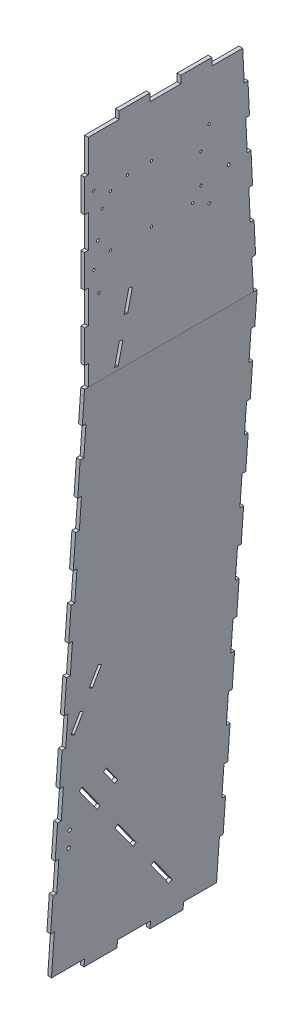
SolidWorks part; units mm, degrees
ref_plane "Front Plane" through (0, 0, 0) normal (0, 0, 1) x (1, 0, 0)
ref_plane "Top Plane" through (0, 0, 0) normal (0, 1, 0) x (1, 0, 0)
ref_plane "Right Plane" through (0, 0, 0) normal (1, 0, 0) x (0, 0, -1)
sketch "Sketch1" plane through (0, 0, 0) normal (0, 0, 1) x (1, 0, 0)
  line L0 (-215.8818, 2052.32) -> (-215.8818, 1463.04)
  line L1 (-215.8818, 1463.04) -> (-316.0886, 20.32)
  line L2 (-316.0886, 20.32) -> (-317.5, 0)
  line L4 (-215.8818, 2052.32) -> (-215.8818, 2072.64)
  line L6 (-215.8818, 2072.64) -> (-205.7153, 2072.64)
  line L7 (-205.7153, 2072.64) -> (-205.7153, 1463.04)
  line L8 (-205.7153, 1463.04) -> (-307.3335, 0)
  line L9 (-317.5, 0) -> (-307.3335, 0)
  line L10 (-371.5407, 0) -> (-280.9748, 0) construction
  line L13 (-371.5407, 20.32) -> (-280.9748, 20.32) construction
  line L15 (-205.7153, 1463.04) -> (205.7153, 1463.04) construction
  point P23 (-305.9221, 20.32)
  dimension "D1" = 307.3335
extrude "Boss-Extrude1" add sketch "Sketch1" against normal blind 469.9
sketch "Sketch2" plane through (-315.9757, 21.9467, 0) normal (-0.9976, 0.0693, 0) x (0, 0, 1)
  line L35 (0, 1355.6785) -> (0, 0.1049)
  line L37 (-234.95, 1444.5652) -> (-234.95, -21.9996) construction
  line L40 (-10.16, 0.1049) -> (0, 0.1049)
  line L43 (-10.16, 0.1049) -> (-10.16, -21.9996)
  line L46 (0, 1272.0274) -> (-10.16, 1272.0274)
  line L47 (-10.16, 1355.6785) -> (-10.16, 1272.0274)
  line L48 (0, 1355.6785) -> (-10.16, 1355.6785)
  line L49 (0, 1177.9051) -> (-10.16, 1177.9051)
  line L50 (-10.16, 1177.9051) -> (-10.16, 1094.2274)
  line L51 (0, 1094.2274) -> (-10.16, 1094.2274)
  line L52 (0, 916.4274) -> (-10.16, 916.4274)
  line L53 (-10.16, 1000.1317) -> (-10.16, 916.4274)
  line L54 (0, 1000.1317) -> (-10.16, 1000.1317)
  line L55 (0, 822.3583) -> (-10.16, 822.3583)
  line L56 (0, 738.6274) -> (-10.16, 738.6274)
  line L57 (-10.16, 822.3583) -> (-10.16, 738.6274)
  line L58 (0, 644.5849) -> (-10.16, 644.5849)
  line L59 (-10.16, 644.5849) -> (-10.16, 560.8274)
  line L60 (0, 560.8274) -> (-10.16, 560.8274)
  line L61 (0, 466.8115) -> (-10.16, 466.8115)
  line L62 (-10.16, 466.8115) -> (-10.16, 383.0274)
  line L63 (0, 383.0274) -> (-10.16, 383.0274)
  line L64 (0, 289.0381) -> (-10.16, 289.0381)
  line L65 (-10.16, 289.0381) -> (-10.16, 205.2274)
  line L66 (0, 205.2274) -> (-10.16, 205.2274)
  line L67 (0, 111.2647) -> (-10.16, 111.2647)
  line L68 (-10.16, 111.2647) -> (-10.16, 0.1049)
  line L69 (0, 0.1049) -> (-10.16, 0.1049)
  line L70 (-10.16, -21.9996) -> (0, -21.9996)
  line L71 (0, 0.1049) -> (0, -21.9996)
  line L72 (-469.9, 1444.5652) -> (0, 1444.5652) construction
  line L73 (-469.9, -21.9996) -> (0, -21.9996) construction
  line L74 (-469.9, 0.1049) -> (-469.9, -21.9996)
  line L75 (-459.74, -21.9996) -> (-469.9, -21.9996)
  line L76 (-469.9, 0.1049) -> (-459.74, 0.1049)
  line L77 (-459.74, 111.2647) -> (-459.74, 0.1049)
  line L78 (-469.9, 111.2647) -> (-459.74, 111.2647)
  line L79 (-469.9, 205.2274) -> (-459.74, 205.2274)
  line L80 (-459.74, 289.0381) -> (-459.74, 205.2274)
  line L81 (-469.9, 289.0381) -> (-459.74, 289.0381)
  line L82 (-469.9, 383.0274) -> (-459.74, 383.0274)
  line L83 (-459.74, 466.8115) -> (-459.74, 383.0274)
  line L84 (-469.9, 466.8115) -> (-459.74, 466.8115)
  line L85 (-469.9, 560.8274) -> (-459.74, 560.8274)
  line L86 (-459.74, 644.5849) -> (-459.74, 560.8274)
  line L87 (-469.9, 644.5849) -> (-459.74, 644.5849)
  line L88 (-459.74, 822.3583) -> (-459.74, 738.6274)
  line L89 (-469.9, 738.6274) -> (-459.74, 738.6274)
  line L90 (-469.9, 822.3583) -> (-459.74, 822.3583)
  line L91 (-469.9, 1000.1317) -> (-459.74, 1000.1317)
  line L92 (-459.74, 1000.1317) -> (-459.74, 916.4274)
  line L93 (-469.9, 916.4274) -> (-459.74, 916.4274)
  line L94 (-469.9, 1094.2274) -> (-459.74, 1094.2274)
  line L95 (-459.74, 1177.9051) -> (-459.74, 1094.2274)
  line L96 (-469.9, 1177.9051) -> (-459.74, 1177.9051)
  line L97 (-469.9, 1355.6785) -> (-459.74, 1355.6785)
  line L98 (-459.74, 1355.6785) -> (-459.74, 1272.0274)
  line L99 (-469.9, 1272.0274) -> (-459.74, 1272.0274)
  line L100 (-459.74, 0.1049) -> (-459.74, -21.9996)
  line L101 (-459.74, 0.1049) -> (-469.9, 0.1049)
  line L102 (-469.9, 1355.6785) -> (-469.9, 0.1049)
  line L103 (-469.9, 1444.5652) -> (-469.9, -21.9996) construction
  line L104 (-459.74, 205.2274) -> (-469.9, 205.2274) construction
  line M1 (0, -21.9996) -> (0, 1444.5652)
  line M3 (-469.9, 1444.5652) -> (-469.9, -21.9996)
  line M4 (-469.9, -21.9996) -> (0, -21.9996)
extrude "Cut-Extrude1" cut sketch "Sketch2" against normal blind 10.16 contours L66 L35 L64 L65 | L69 L67 L68 M1 | L60 L35 L58 L59 | L63 L35 L61 L62 | L55 L57 L56 L35 | L35 L54 L53 L52 | L51 L35 L49 L50 | L35 L48 L47 L46 | L40 L43 M4 M1 | L100 L76 M3 M4 | L78 L76 L77 M3 | L81 L79 L80 M3 | L84 L82 L83 M3 | L87 L85 L86 M3 | L90 L89 L88 M3 | L93 L92 L91 M3 | L96 L94 L95 M3 | L99 L98 L97 M3 region at (-224.9388, 1332.6419, -464.82) region at (-237.2577, 1155.2825, -464.82) region at (-249.5765, 977.9231, -464.82) region at (-261.8953, 800.5637, -464.82) region at (-274.2142, 623.2043, -464.82) region at (-286.533, 445.8449, -464.82) region at (-298.8518, 268.4855, -464.82) region at (-316.7342, 11.0257, -464.82) region at (-312.1173, 77.4977, -5.08) region at (-298.8518, 268.4855, -5.08) region at (-286.533, 445.8449, -5.08) region at (-274.2142, 623.2043, -5.08) region at (-261.8953, 800.5637, -5.08) region at (-249.5765, 977.9231, -5.08) region at (-237.2577, 1155.2825, -5.08) region at (-224.9388, 1332.6419, -5.08) region at (-316.7342, 11.0257, -5.08) region at (-312.1173, 77.4977, -464.82)
sketch "Sketch3" plane through (-215.8818, 0, 0) normal (-1, 0, 0) x (0, 0, 1)
  line L0 (0, 2052.32) -> (-10.16, 2052.32) construction
  line L1 (0, 1963.42) -> (-10.16, 1963.42) construction
  line L2 (-10.16, 2052.32) -> (-10.16, 1963.42) construction
  line L3 (0, 1874.52) -> (-10.16, 1874.52) construction
  line L4 (0, 1463.04) -> (0, 2072.64)
  line L5 (0, 2072.64) -> (-469.9, 2072.64)
  line L6 (-469.9, 2072.64) -> (-469.9, 1463.04)
  line L8 (0, 1463.04) -> (0, 2072.64)
  line L9 (0, 2072.64) -> (-469.9, 2072.64)
  line L12 (0, 1785.62) -> (-10.16, 1785.62) construction
  line L13 (-10.16, 1874.52) -> (-10.16, 1785.62) construction
  line L14 (0, 1696.72) -> (-10.16, 1696.72) construction
  line L15 (0, 1607.82) -> (-10.16, 1607.82) construction
  line L16 (-10.16, 1696.72) -> (-10.16, 1607.82) construction
  line L17 (0, 1518.92) -> (-10.16, 1518.92) construction
  line L18 (-10.16, 1518.92) -> (-10.16, 1488.44) construction
  line L19 (0, 2052.32) -> (-10.16, 2052.32)
  line L20 (0, 1963.42) -> (-10.16, 1963.42)
  line L21 (-10.16, 2052.32) -> (-10.16, 1963.42)
  line L22 (0, 1874.52) -> (-10.16, 1874.52)
  line L23 (0, 1785.62) -> (-10.16, 1785.62)
  line L24 (-10.16, 1874.52) -> (-10.16, 1785.62)
  line L25 (0, 1696.72) -> (-10.16, 1696.72)
  line L26 (0, 1607.82) -> (-10.16, 1607.82)
  line L27 (-10.16, 1696.72) -> (-10.16, 1607.82)
  line L28 (0, 1518.92) -> (-10.16, 1518.92)
  line L29 (-10.16, 1518.92) -> (-10.16, 1488.44)
  line L30 (0, 2052.32) -> (0, 1463.04)
  line L31 (-234.95, 1463.04) -> (-234.95, 2072.64) construction
  line L32 (-10.16, 2052.32) -> (0, 2052.32)
  line L33 (-10.16, 2052.32) -> (-10.16, 2072.64)
  line L34 (-10.16, 2072.64) -> (0, 2072.64)
  line L35 (0, 2052.32) -> (0, 2072.64)
  line L36 (-469.9, 1463.04) -> (-439.9, 2072.64)
  line L37 (-469.9, 1463.04) -> (-465.7536, 1547.2942)
  line L38 (-469.9, 1463.04) -> (-459.7523, 1462.5406)
  line L39 (-465.7536, 1547.2942) -> (-455.6059, 1546.7948)
  line L40 (-459.7523, 1462.5406) -> (-455.6059, 1546.7948)
  line L41 (-465.7536, 1547.2942) -> (-455.6059, 1546.7948)
  line L42 (-465.7536, 1547.2942) -> (-461.6073, 1631.5484)
  line L43 (-455.6059, 1546.7948) -> (-451.4595, 1631.049)
  line L44 (-461.6073, 1631.5484) -> (-451.4595, 1631.049)
  line L45 (-461.6073, 1631.5484) -> (-451.4595, 1631.049)
  line L46 (-461.6073, 1631.5484) -> (-457.4609, 1715.8026)
  line L47 (-451.4595, 1631.049) -> (-447.3132, 1715.3032)
  line L48 (-457.4609, 1715.8026) -> (-447.3132, 1715.3032)
  line L49 (-457.4609, 1715.8026) -> (-447.3132, 1715.3032)
  line L50 (-457.4609, 1715.8026) -> (-453.3145, 1800.0568)
  line L51 (-447.3132, 1715.3032) -> (-443.1668, 1799.5574)
  line L52 (-453.3145, 1800.0568) -> (-443.1668, 1799.5574)
  line L53 (-453.3145, 1800.0568) -> (-443.1668, 1799.5574)
  line L54 (-10.16, 1488.44) -> (-10.16, 1463.04)
  line L56 (-453.3145, 1800.0568) -> (-449.1682, 1884.311)
  line L57 (-443.1668, 1799.5574) -> (-439.0204, 1883.8116)
  line L58 (-449.1682, 1884.311) -> (-439.0204, 1883.8116)
  line L59 (-449.1682, 1884.311) -> (-439.0204, 1883.8116)
  line L60 (-449.1682, 1884.311) -> (-445.0218, 1968.5652)
  line L61 (-439.0204, 1883.8116) -> (-434.8741, 1968.0658)
  line L62 (-445.0218, 1968.5652) -> (-434.8741, 1968.0658)
  line L63 (-10.16, 2052.32) -> (-469.9, 2052.32) construction
  line L64 (-469.9, 2072.64) -> (-469.9, 1463.04) construction
  line L65 (-445.0218, 1968.5652) -> (-434.8741, 1968.0658)
  line L66 (-445.0218, 1968.5652) -> (-440.8754, 2052.8194)
  line L67 (-434.8741, 1968.0658) -> (-430.7277, 2052.32)
  line L68 (-440.8754, 2052.8194) -> (-430.7277, 2052.32)
  line L69 (-430.7277, 2052.32) -> (-440.9, 2052.32)
  line L70 (-440.8754, 2052.8194) -> (-430.7277, 2052.32)
  line L71 (-440.8754, 2052.8194) -> (-439.4854, 2081.0647)
  line L72 (-430.7277, 2052.32) -> (-429.3377, 2080.5653)
  line L73 (-439.4854, 2081.0647) -> (-429.3377, 2080.5653)
  line L74 (-469.9, 1463.04) -> (0, 1463.04) construction
  line L78 (-469.9, 1463.04) -> (0, 1463.04)
  line L79 (-469.9, 1463.04) -> (0, 1463.04)
  line M7 (0, 1463.04) -> (0, 2072.64)
  line M8 (0, 2072.64) -> (-469.9, 2072.64)
  line M9 (-469.9, 2072.64) -> (-469.9, 1463.04)
  line M10 (-469.9, 1463.04) -> (0, 1463.04)
  dimension "D2" = 30
  dimension "D3" = 10.16
  dimension "D1" = 0
extrude "Cut-Extrude2" cut sketch "Sketch3" against normal blind 12.7 contours M10 | L29 L54 L28 M10 M7 | L36 L66 M9 M8 | L48 L36 L44 L47 | L58 L36 L52 L57 | L67 L69 L36 L62 | L25 L27 L26 L8 | L22 L24 L23 L8 | L19 L21 L20 L8 | L33 L19 L8 M8 | L68 L72 L36 M8 | L69 L68 L66 region at (-215.8818, 1490.98, -5.08) region at (-215.8818, 1652.27, -5.08) region at (-215.8818, 1505.0424, -462.7518) region at (-215.8818, 1869.44, -459.9) region at (-215.8818, 1830.07, -5.08) region at (-215.8818, 1673.4258, -454.4602) region at (-215.8818, 2062.6043, -435.2866) region at (-215.8818, 2007.87, -5.08) region at (-215.8818, 1841.9342, -446.1675) region at (-215.8818, 2052.4865, -437.501) region at (-215.8818, 2062.48, -5.08) region at (-215.8818, 2010.3176, -437.8759)
sketch "Sketch4" plane through (-215.8818, 0, 0) normal (-1, 0, 0) x (0, 0, 1)
  line L1 (-430.7277, 2072.64) -> (-346.6142, 2072.64)
  line L2 (-430.7277, 2072.64) -> (-430.7277, 2052.32)
  line L3 (-430.7277, 2052.32) -> (-346.6142, 2052.32)
  line L4 (-346.6142, 2072.64) -> (-346.6142, 2052.32)
  line L5 (-10.16, 2072.64) -> (-10.16, 1963.42) construction
  line L6 (-346.6142, 2072.64) -> (-262.5006, 2072.64)
  line L7 (-346.6142, 2072.64) -> (-346.6142, 2052.32)
  line L8 (-346.6142, 2052.32) -> (-262.5006, 2052.32)
  line L9 (-262.5006, 2072.64) -> (-262.5006, 2052.32)
  line L10 (-262.5006, 2072.64) -> (-178.3871, 2072.64)
  line L11 (-262.5006, 2072.64) -> (-262.5006, 2052.32)
  line L12 (-262.5006, 2052.32) -> (-178.3871, 2052.32)
  line L13 (-178.3871, 2072.64) -> (-178.3871, 2052.32)
  line L14 (-178.3871, 2072.64) -> (-94.2735, 2072.64)
  line L15 (-178.3871, 2072.64) -> (-178.3871, 2052.32)
  line L16 (-178.3871, 2052.32) -> (-94.2735, 2052.32)
  line L17 (-94.2735, 2072.64) -> (-94.2735, 2052.32)
  line L18 (-94.2735, 2072.64) -> (-10.16, 2072.64)
  line L19 (-94.2735, 2072.64) -> (-94.2735, 2052.32)
  line L20 (-94.2735, 2052.32) -> (-10.16, 2052.32)
  line L21 (-10.16, 2072.64) -> (-10.16, 2052.32)
  line L23 (-434.8741, 1968.0658) -> (-429.7277, 2072.64) construction
  line L24 (-429.7277, 2072.64) -> (-10.16, 2072.64) construction
  line M26 (-10.16, 1963.42) -> (-10.16, 2072.64)
  line M27 (-10.16, 2072.64) -> (-429.7277, 2072.64)
  dimension "D1" = 20.32
extrude "Cut-Extrude3" cut sketch "Sketch4" against normal blind 12.7 contours L4 L3 M27 | L13 L9 L12 M27 | L17 L20 M26 M27 region at (-215.8818, 2062.48, -388.6709) region at (-215.8818, 2062.48, -220.4439) region at (-215.8818, 2062.48, -52.2168)
sketch "Sketch5" plane through (-315.9757, 21.9467, 0) normal (-0.9976, 0.0693, 0) x (0, 0, 1)
  line L1 (-459.74, -21.9996) -> (-369.824, -21.9996)
  line L2 (-459.74, -21.9996) -> (-459.74, -1.6796)
  line L3 (-459.74, -1.6796) -> (-369.824, -1.6796)
  line L4 (-369.824, -21.9996) -> (-369.824, -1.6796)
  line L5 (-369.824, -21.9996) -> (-279.908, -21.9996)
  line L6 (-369.824, -21.9996) -> (-369.824, -1.6796)
  line L7 (-369.824, -1.6796) -> (-279.908, -1.6796)
  line L8 (-279.908, -21.9996) -> (-279.908, -1.6796)
  line L9 (-279.908, -21.9996) -> (-189.992, -21.9996)
  line L10 (-279.908, -21.9996) -> (-279.908, -1.6796)
  line L11 (-279.908, -1.6796) -> (-189.992, -1.6796)
  line L12 (-189.992, -21.9996) -> (-189.992, -1.6796)
  line L13 (-189.992, -21.9996) -> (-100.076, -21.9996)
  line L14 (-189.992, -21.9996) -> (-189.992, -1.6796)
  line L15 (-189.992, -1.6796) -> (-100.076, -1.6796)
  line L16 (-100.076, -21.9996) -> (-100.076, -1.6796)
  line L17 (-100.076, -21.9996) -> (-10.16, -21.9996)
  line L18 (-100.076, -21.9996) -> (-100.076, -1.6796)
  line L19 (-100.076, -1.6796) -> (-10.16, -1.6796)
  line L20 (-10.16, -21.9996) -> (-10.16, -1.6796)
  line L21 (-10.16, 111.2647) -> (-10.16, -21.9996) construction
  dimension "D1" = 20.32
extrude "Cut-Extrude4" cut sketch "Sketch5" against normal blind 12.7 contours L1 L4 L3 L2 | L9 L12 L11 L8 | L17 L20 L19 L18 L16 region at (-316.796, 10.1356, -414.782) region at (-316.796, 10.1356, -234.95) region at (-316.796, 10.1356, -55.118)
sketch "Sketch6" plane through (-315.9757, 21.9467, 0) normal (-0.9976, 0.0693, 0) x (0, 0, 1)
  line L0 (-217.3726, 211.9965) -> (-163.4402, 285.2141)
  line L1 (-325.2304, 65.5562) -> (-271.298, 138.7738)
  line L2 (-44.1085, 632.6765) -> (-22.5289, 586.4358) construction
  line L3 (-74.8989, 674.6188) -> (-65.6881, 678.9173) construction
  line L8 (-271.6486, 139.032) -> (-279.8219, 145.0526) construction
  line L56 (-87.2678, 725.158) -> (-65.6881, 678.9173) construction
  line L57 (-74.8989, 674.6188) -> (-96.4785, 720.8595) construction
  line L58 (-31.7396, 582.1373) -> (-22.5289, 586.4358) construction
  line L59 (-31.7396, 582.1373) -> (-53.3192, 628.3781) construction
  line L60 (-53.3192, 628.3781) -> (-44.1085, 632.6765) construction
  line L63 (-117.6881, 364.4573) -> (-63.7557, 437.6749) construction
  line L65 (-225.5528, 218.0222) -> (-171.6205, 291.2397) construction
  line L69 (-333.4176, 71.587) -> (-279.4852, 144.8046) construction
  line L70 (-109.5008, 358.4266) -> (-55.5685, 431.6442)
  line L71 (-44.1085, 632.6765) -> (-22.5289, 586.4358)
  line L72 (-74.8989, 674.6188) -> (-65.6881, 678.9173)
  line L73 (-87.2678, 725.158) -> (-65.6881, 678.9173)
  line L74 (-74.8989, 674.6188) -> (-96.4785, 720.8595)
  line L75 (-31.7396, 582.1373) -> (-22.5289, 586.4358)
  line L76 (-31.7396, 582.1373) -> (-53.3192, 628.3781)
  line L77 (-53.3192, 628.3781) -> (-44.1085, 632.6765)
  line L78 (-109.5008, 358.4266) -> (-117.6881, 364.4573)
  line L79 (-55.5685, 431.6442) -> (-63.7557, 437.6749)
  line L80 (-117.6881, 364.4573) -> (-63.7557, 437.6749)
  line L81 (-163.4402, 285.2141) -> (-171.6205, 291.2397)
  line L82 (-225.5528, 218.0222) -> (-171.6205, 291.2397)
  line L83 (-217.3726, 211.9965) -> (-225.5528, 218.0222)
  line L84 (-271.298, 138.7738) -> (-279.4852, 144.8046)
  line L85 (-325.2304, 65.5562) -> (-333.4176, 71.587)
  line L86 (-333.4176, 71.587) -> (-279.4852, 144.8046)
  line L87 (-87.2678, 725.158) -> (-96.4785, 720.8595)
  line L89 (-109.8514, 358.6848) -> (-118.0248, 364.7053) construction
  line L90 (-163.7838, 285.4672) -> (-171.9572, 291.4877) construction
  line L91 (-217.7162, 212.2496) -> (-225.8895, 218.2702) construction
  dimension "D1" = 10.16
sketch "Sketch8" plane through (-215.8818, 0, 0) normal (-1, 0, 0) x (0, 0, 1)
  circle A0 centre (-450.215, 1043.94) radius 9.525 construction
  circle A1 centre (-450.215, 1043.94) radius 9.525
sketch "Sketch13" plane through (-215.8818, 0, 0) normal (-1, 0, 0) x (0, 0, 1)
  line L0 (-413.556, 1633.6344) -> (-413.556, 1614.5844) construction
  line L1 (-270.8715, 1611.4094) -> (-270.8715, 1636.8094) construction
  line L2 (-413.556, 1624.1094) -> (-270.8715, 1624.1094) construction
  line L3 (-270.8715, 1624.1094) -> (-400.856, 1624.1094) construction
  line L4 (-270.8715, 1605.0594) -> (-400.856, 1605.0594) construction
  line L5 (-270.8715, 1643.1594) -> (-400.856, 1643.1594) construction
  line L6 (-416.7447, 2052.32) -> (-335.4278, 2052.32)
  line L7 (-422.8907, 1968.0316) -> (-416.7447, 2052.32)
  circle A0 centre (-25.2465, 1731.87) radius 3.175
  circle A1 centre (-70.409, 1755.42) radius 3.175
  circle A2 centre (-182.409, 1755.42) radius 3.175
  circle A3 centre (-25.2465, 1918.97) radius 3.175
  circle A4 centre (-47.789, 1865.42) radius 3.175
  circle A5 centre (-182.409, 1910.42) radius 3.175
  circle A6 centre (-117.079, 1910.42) radius 3.175
  circle A7 centre (-70.409, 1895.42) radius 3.175
  circle A8 centre (-317.029, 1865.42) radius 3.175
  circle A9 centre (-294.409, 1755.42) radius 3.175
  circle A10 centre (-317.029, 1785.42) radius 3.175
  circle A11 centre (-339.5715, 1731.87) radius 3.175
  circle A12 centre (-339.5715, 1918.97) radius 3.175
  arc A13 (-270.8715, 1605.0594) -> (-270.8715, 1643.1594) centre (-270.8715, 1624.1094) ccw construction
  arc A14 (-400.856, 1643.1594) -> (-400.856, 1605.0594) centre (-400.856, 1624.1094) ccw construction
  point P34 (-335.8637, 1624.1094)
  point P42 (-430.7277, 2052.32)
  dimension "D1" = 12.7
  dimension "D2" = 19.05
extrude "Cut-Extrude8" cut sketch "Sketch13" against normal through all contours L5 A14 L4 A13 | A11 | A10 | A9 | A2 | A1 | A0 | A4 | A7 | A6 | A3 | A5 | A8 | A12 | L0 A14 region at (-215.8818, 1731.87, -25.2465) region at (-215.8818, 1755.42, -70.409) region at (-215.8818, 1755.42, -182.409) region at (-215.8818, 1918.97, -25.2465) region at (-215.8818, 1865.42, -47.789) region at (-215.8818, 1910.42, -182.409) region at (-215.8818, 1910.42, -117.079) region at (-215.8818, 1895.42, -70.409) region at (-215.8818, 1865.42, -317.029) region at (-215.8818, 1755.42, -294.409) region at (-215.8818, 1785.42, -317.029) region at (-215.8818, 1731.87, -339.5715) region at (-215.8818, 1918.97, -339.5715)
sketch "Sketch17" plane through (-215.8818, 0, 0) normal (-1, 0, 0) x (0, 0, 1)
  line L0 (-130.4243, 1639.6605) -> (-120.5247, 1641.946)
  line L1 (-120.5247, 1641.946) -> (-107.584, 1585.8939)
  line L2 (-130.4243, 1639.6605) -> (-117.4836, 1583.6084)
  line L3 (-117.4836, 1583.6084) -> (-107.584, 1585.8939)
  line L4 (-104.543, 1527.5563) -> (-94.6434, 1529.8418)
  line L5 (-91.6023, 1471.5043) -> (-104.543, 1527.5563)
  line L6 (-91.6023, 1471.5043) -> (-81.7027, 1473.7898)
  line L7 (-81.7027, 1473.7898) -> (-94.6434, 1529.8418)
  line L8 (-416.7447, 2052.32) -> (-335.4278, 2052.32)
  line L9 (-422.8907, 1968.0316) -> (-416.7447, 2052.32)
  point P11 (-430.7277, 2052.32)
extrude "Cut-Extrude9" cut sketch "Sketch17" against normal through all contours L6 L7 L4 L5 | L2 L3 L1 L0 region at (-215.8818, 1612.7772, -119.0041) region at (-215.8818, 1500.6731, -93.1229)
sketch "Sketch20" plane through (-315.9757, 21.9467, 0) normal (-0.9976, 0.0693, 0) x (0, 0, 1)
  line L0 (-441.6805, 375.8656) -> (-258.1103, 563.7707)
  line L1 (-258.1103, 563.7707) -> (-341.7803, 797.9819)
  line L2 (-258.1103, 563.7707) -> (-10.16, 315.8204)
  line L3 (-258.1103, 563.7707) -> (-258.6478, 797.9819)
  line L8 (-10.16, 110.1771) -> (-10.16, -1.6796)
  line L9 (-10.16, 466.8115) -> (-10.16, 383.0274) construction
  line L10 (-13.335, 290.1376) -> (-13.335, 359.9876)
  line L11 (-13.335, 290.1376) -> (-48.26, 290.1376)
  line L12 (-13.335, 359.9876) -> (-48.26, 359.9876)
  line L13 (-48.26, 290.1376) -> (-48.26, 359.9876)
  line L32 (-120.9293, 445.7124) -> (-154.8235, 399.6982)
  line L33 (-120.9293, 445.7124) -> (-128.5983, 451.3614)
  line L34 (-154.8235, 399.6982) -> (-162.4926, 405.3473)
  line L35 (-128.5983, 451.3614) -> (-162.4926, 405.3473)
  line L37 (-109.5008, 358.4266) -> (-117.6881, 364.4573) construction
  line L38 (-117.6881, 364.4573) -> (-63.7557, 437.6749) construction
  line L39 (-137.8764, 422.7053) -> (43.6586, 288.9858) construction
  line L40 (-35.56, 332.8883) -> (-35.56, 361.687) construction
  line L41 (-10.16, 466.8115) -> (-10.16, 383.0274)
  circle A0 centre (-35.56, 347.2876) radius 4.7625
  circle A2 centre (-35.56, 302.8376) radius 4.7625
  point P11 (-10.16, -1.6796)
  point P57 (-35.56, 341.2204)
  dimension "D9" = 44.45
  dimension "D15" = 9.525
  dimension "D3" = 3.175
  dimension "D4" = 12.7
  dimension "D5" = 57.15
  dimension "D6" = 317.5
  dimension "D7" = 12.7
  dimension "D8" = 12.7
  dimension "D22" = 9.525
  dimension "D23" = 6.35
  dimension "D24" = 50.8
  dimension "D25" = 34.925
extrude "Cut-Extrude10" cut sketch "Sketch20" against normal through all contours A2 | L2 A0 | L2 A0 | L2 L35 L34 L32 | L33 L35 L2 L32 region at (-285.2619, 464.1454, -128.5379) region at (-286.8509, 441.2683, -145.572) region at (-291.908, 368.4591, -35.5004) region at (-292.1316, 365.2395, -38.7278) region at (-294.992, 324.0565, -35.56)
sketch "Sketch22" [suppressed] plane through (-315.9757, 21.9467, 0) normal (-0.9976, 0.0693, 0) x (0, 0, 1)
  line L3 (-138.6114, 421.183) -> (-138.6114, 431.343)
  line L4 (-138.6114, 431.343) -> (-202.8371, 431.343)
  line L5 (-138.6114, 421.183) -> (-202.8371, 421.183)
  line L6 (-202.8371, 421.183) -> (-202.8371, 431.343)
  line L7 (-267.0629, 421.183) -> (-267.0629, 431.343)
  line L8 (-267.0629, 431.343) -> (-331.2886, 431.343)
  line L9 (-267.0629, 421.183) -> (-331.2886, 421.183)
  line L10 (-331.2886, 421.183) -> (-331.2886, 431.343)
  line L11 (-395.5143, 421.183) -> (-395.5143, 431.343)
  line L12 (-395.5143, 421.183) -> (-459.74, 421.183)
  line L13 (-395.5143, 431.343) -> (-459.74, 431.343)
  line L15 (-459.74, 421.183) -> (-459.74, 431.343)
  line L16 (-100.076, -1.6796) -> (-10.16, -1.6796) construction
  line L17 (-10.16, 111.2647) -> (-10.16, -1.6796) construction
  line L18 (-100.076, -1.6796) -> (-10.16, -1.6796)
  line L19 (-10.16, 111.2647) -> (-10.16, -1.6796)
  point P0 (-10.16, -1.6796)
sketch "Sketch23" plane through (-315.9757, 21.9467, 0) normal (-0.9976, 0.0693, 0) x (0, 0, 1)
  line L2 (-450.215, 1024.4555) -> (-396.5689, 1024.4555) construction
  line L3 (-437.515, 986.3555) -> (-437.515, 1062.5555) construction
  circle A0 centre (-437.515, 986.3555) radius 3.175
  circle A1 centre (-421.64, 1024.4555) radius 3.175
  circle A2 centre (-437.515, 1062.5555) radius 3.175
  point P21 (-437.515, 1024.4555)
  dimension "D1" = 6.35
  dimension "D2" = 28.575
  dimension "D3" = 76.2
  dimension "D4" = 12.7
sketch "Sketch24" plane through (-215.8818, 0, 0) normal (-1, 0, 0) x (0, 0, 1)
  line L0 (-10.16, 1696.72) -> (-10.16, 1607.82) construction
  line L1 (0, 1696.72) -> (-10.16, 1696.72) construction
  circle A0 centre (-39.3138, 1670.4542) radius 18 construction
  circle A1 centre (-39.3138, 1670.4542) radius 18 construction
  circle A2 centre (-39.3137, 1670.4542) radius 3.175
  dimension "D1" = 6.35
  dimension "D2" = 29.1537
  dimension "D3" = 26.2658
extrude "Cut-Extrude12" cut sketch "Sketch24" against normal blind 12.7
sketch "Sketch26" plane through (-215.8818, 0, 0) normal (-1, 0, 0) x (0, 0, 1)
  line L4 (-74.8989, 694.9441) -> (-65.6881, 699.2322)
  line L5 (-65.6881, 699.2322) -> (-87.2678, 745.3618)
  line L6 (-87.2678, 745.3618) -> (-96.4785, 741.0737)
  line L7 (-96.4785, 741.0737) -> (-74.8989, 694.9441)
  line L8 (-74.8989, 694.9441) -> (-65.6881, 699.2322)
  line L9 (-65.6881, 699.2322) -> (-87.2678, 745.3618)
  line L10 (-87.2678, 745.3618) -> (-96.4785, 741.0737)
  line L11 (-96.4785, 741.0737) -> (-74.8989, 694.9441)
  line L12 (-22.5289, 606.973) -> (-44.1085, 653.1026)
  line L13 (-31.7396, 602.6849) -> (-22.5289, 606.973)
  line L14 (-53.3192, 648.8145) -> (-31.7396, 602.6849)
  line L15 (-44.1085, 653.1026) -> (-53.3192, 648.8145)
  line L16 (-22.5289, 606.973) -> (-44.1085, 653.1026)
  line L17 (-31.7396, 602.6849) -> (-22.5289, 606.973)
  line L18 (-53.3192, 648.8145) -> (-31.7396, 602.6849)
  line L19 (-44.1085, 653.1026) -> (-53.3192, 648.8145)
  line L20 (-117.6881, 385.5281) -> (-109.5008, 379.5118)
  line L21 (-63.7557, 458.5697) -> (-117.6881, 385.5281)
  line L22 (-55.5685, 452.5534) -> (-63.7557, 458.5697)
  line L23 (-109.5008, 379.5118) -> (-55.5685, 452.5534)
  line L24 (-117.6881, 385.5281) -> (-109.5008, 379.5118)
  line L25 (-63.7557, 458.5697) -> (-117.6881, 385.5281)
  line L26 (-55.5685, 452.5534) -> (-63.7557, 458.5697)
  line L27 (-109.5008, 379.5118) -> (-55.5685, 452.5534)
  line L28 (-325.2304, 87.3454) -> (-271.298, 160.387)
  line L29 (-271.298, 160.387) -> (-279.4852, 166.4032)
  line L30 (-279.4852, 166.4032) -> (-333.4176, 93.3616)
  line L31 (-333.4176, 93.3616) -> (-325.2304, 87.3454)
  line L32 (-325.2304, 87.3454) -> (-271.298, 160.387)
  line L33 (-271.298, 160.387) -> (-279.4852, 166.4032)
  line L34 (-279.4852, 166.4032) -> (-333.4176, 93.3616)
  line L35 (-333.4176, 93.3616) -> (-325.2304, 87.3454)
  line L36 (-217.3726, 233.4337) -> (-163.4402, 306.4753)
  line L37 (-163.4402, 306.4753) -> (-171.6205, 312.4864)
  line L38 (-171.6205, 312.4864) -> (-225.5528, 239.4448)
  line L39 (-225.5528, 239.4448) -> (-217.3726, 233.4337)
  line L40 (-217.3726, 233.4337) -> (-163.4402, 306.4753)
  line L41 (-163.4402, 306.4753) -> (-171.6205, 312.4864)
  line L42 (-171.6205, 312.4864) -> (-225.5528, 239.4448)
  line L43 (-225.5528, 239.4448) -> (-217.3726, 233.4337)
  dimension "D1" = 0
  dimension "D2" = 0
  dimension "D3" = 0
  dimension "D4" = 0
  dimension "D5" = 0
extrude "Cut-Extrude13" cut sketch "Sketch26" along normal through all both and the other way through all contours L24 L27 L26 L25 | L42 L43 L40 L41 | L16 L19 L18 L17 | L8 L9 L10 L11 | L34 L35 L32 L33 region at (-215.8818, 419.0407, -86.6283) region at (-215.8818, 272.9601, -194.4965)
sketch "Sketch28" plane through (0, 0, 0) normal (0, -1, 0) x (1, 0, 0)
  line L0 (-317.5, -369.824) -> (-307.3335, -369.824) construction
  line L1 (-307.3335, -369.824) -> (-307.3335, -279.908) construction
  line L2 (-307.3335, -279.908) -> (-317.5, -279.908) construction
  line L3 (-317.5, -279.908) -> (-317.5, -369.824) construction
  line L4 (-317.5, -189.992) -> (-307.3335, -189.992) construction
  line L5 (-307.3335, -189.992) -> (-307.3335, -100.076) construction
  line L6 (-307.3335, -100.076) -> (-317.5, -100.076) construction
  line L7 (-317.5, -100.076) -> (-317.5, -189.992) construction
  line L8 (-317.5, -369.824) -> (-307.3335, -369.824)
  line L9 (-307.3335, -369.824) -> (-307.3335, -279.908)
  line L10 (-307.3335, -279.908) -> (-317.5, -279.908)
  line L11 (-317.5, -279.908) -> (-317.5, -369.824)
  line L12 (-317.5, -189.992) -> (-307.3335, -189.992)
  line L13 (-307.3335, -189.992) -> (-307.3335, -100.076)
  line L14 (-307.3335, -100.076) -> (-317.5, -100.076)
  line L15 (-317.5, -100.076) -> (-317.5, -189.992)
sketch "Sketch29" plane through (-215.8818, 0, 0) normal (-1, 0, 0) x (0, 0, 1)
  line L0 (-409.7277, 1463.04) -> (-459.7277, 1463.04)
  line L1 (-459.7277, 1463.04) -> (-457.27, 1512.9796)
  line L2 (-459.7277, 1463.04) -> (-455.6059, 1546.7948) construction
  circle A0 centre (-459.7277, 1463.04) radius 50
  dimension "D1" = 100
extrude "Cut-Extrude15" [suppressed] cut sketch "Sketch29" against normal through all both contours L0 A0 L1
sketch "Sketch30" plane through (-205.7153, 0, 0) normal (1, 0, 0) x (0, 0, -1)
  line L0 (10.16, 1785.62) -> (10.16, 1874.52) construction
  line L1 (10.16, 1785.62) -> (0, 1785.62) construction
  circle A0 centre (36.16, 1796.1325) radius 4
  circle A1 centre (392.66, 1796.1325) radius 4
  dimension "D1" = 8
  dimension "D2" = 26
  dimension "D4" = 356.5
  dimension "D5" = 8
  dimension "D3" = 10.5125
extrude "Cut-Extrude16" cut sketch "Sketch30" against normal blind 18
